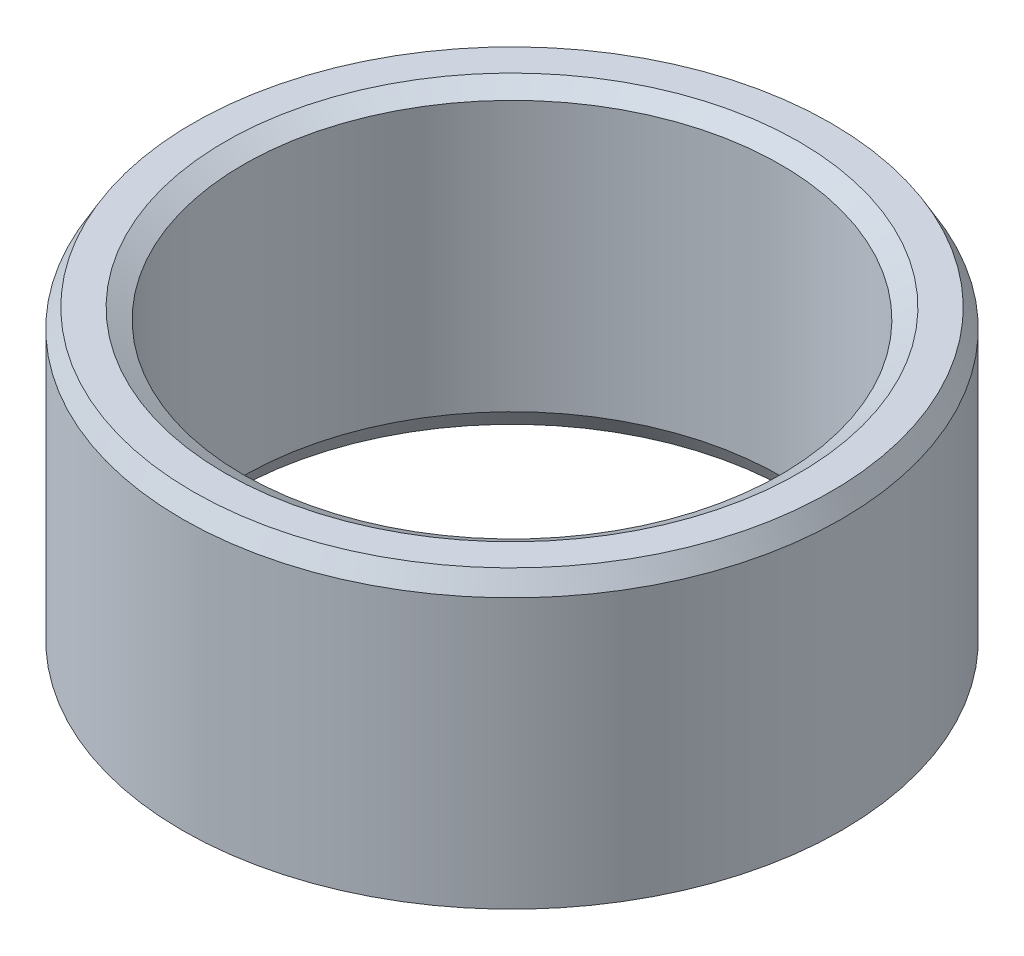
SolidWorks part; units mm, degrees
ref_plane "Front Plane" through (0, 0, 0) normal (0, 0, 1) x (1, 0, 0)
ref_plane "Top Plane" through (0, 0, 0) normal (0, 1, 0) x (1, 0, 0)
ref_plane "Right Plane" through (0, 0, 0) normal (1, 0, 0) x (0, 0, -1)
sketch "Sketch1" plane through (0, 0, 0) normal (0, 1, 0) x (1, 0, 0)
  circle A0 centre (0, 0) radius 22.5
  dimension "SLEEVE_OD" = 45
extrude "Boss-Extrude1" add sketch "Sketch1" along normal blind 20.3849
sketch "Sketch2" plane through (0, 0, 0) normal (0, 1, 0) x (1, 0, 0)
  circle A0 centre (0, 0) radius 18.3322
  dimension "BORE_D" = 36.6644
extrude "Cut-Extrude1" cut sketch "Sketch2" along normal through all
chamfer "Chamfer1" distance 1.2564 angle 30 4 edges at (0, 20.3849, 18.3322) (0, 0, 18.3322) (0, 0, 22.5) (0, 20.3849, 22.5) first distance on face at (0, 20.3849, 18.3322) first distance on face at (0, 0, 18.3322) first distance on face at (0, 20.3849, 22.5)
